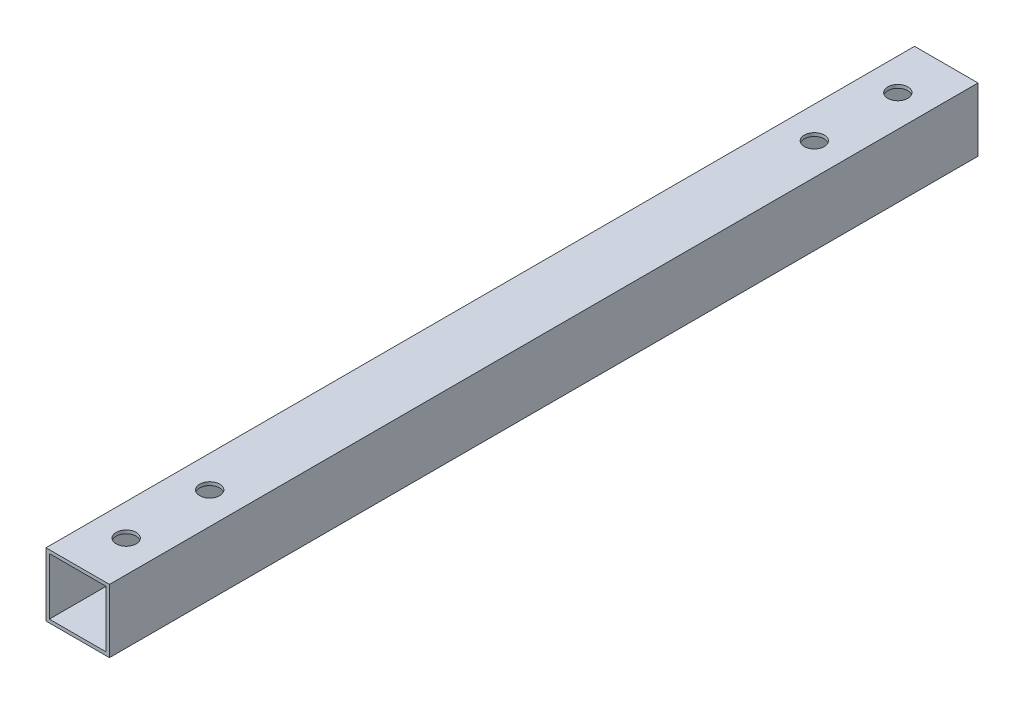
SolidWorks part; units mm, degrees
ref_plane "Plano frontal" through (0, 0, 0) normal (0, 0, 1) x (1, 0, 0)
ref_plane "Plano superior" through (0, 0, 0) normal (0, 1, 0) x (1, 0, 0)
ref_plane "Plano direito" through (0, 0, 0) normal (1, 0, 0) x (0, 0, -1)
sketch "Esboço1" plane through (0, 0, 0) normal (0, 0, 1) x (1, 0, 0)
  line L1 (-9.5, 9.5) -> (9.5, 9.5)
  line L2 (-9.5, 9.5) -> (-9.5, -9.5)
  line L3 (-9.5, -9.5) -> (9.5, -9.5)
  line L4 (9.5, 9.5) -> (9.5, -9.5)
  line L5 (-9.5, 9.5) -> (9.5, -9.5) construction
  line L6 (-9.5, -9.5) -> (9.5, 9.5) construction
  line L11 (-5.6574, 5.6574) -> (5.6574, -5.6574) construction
  line L12 (-5.6574, -5.6574) -> (5.6574, 5.6574) construction
  point P0 (0, 0)
  point P6 (0, 0)
  dimension "D1" = 19
extrude "Ressalto-extrusão1" add sketch "Esboço1" along normal blind 260
shell "Casca2" thickness 1 removed face at (0, 0, 0) removed face at (0, 0, 260)
sketch "Esboço2" plane through (0, 9.5, 0) normal (0, 1, 0) x (1, 0, 0)
  circle A4 centre (0, -220.5) radius 3
  circle A5 centre (0, -245.5) radius 3
  circle A6 centre (0, -14.5) radius 3
  circle A7 centre (0, -39.5) radius 3
extrude "Corte-extrusão1" cut sketch "Esboço2" against normal through all
